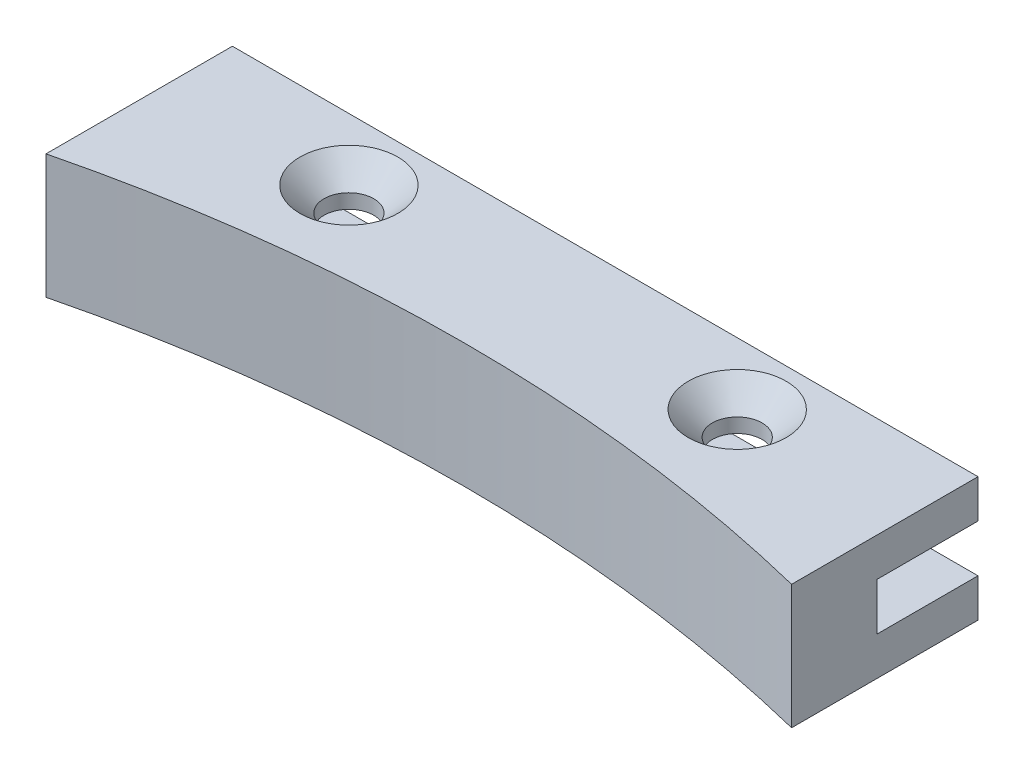
SolidWorks part; units mm, degrees
material "6061-T6 (SS)"
ref_plane "Front Plane" through (0, 0, 0) normal (0, 0, 1) x (1, 0, 0)
ref_plane "Top Plane" through (0, 0, 0) normal (0, 1, 0) x (1, 0, 0)
ref_plane "Right Plane" through (0, 0, 0) normal (1, 0, 0) x (0, 0, -1)
sketch "Sketch1" plane through (0, 0, 0) normal (0, 1, 0) x (1, 0, 0)
  line L0 (-24, 0) -> (24, 0)
  line L1 (24, 0) -> (24, -12)
  line L2 (-24, 0) -> (-24, -12)
  line L3 (-24, -9.0773) -> (24, -9.0773) construction
  line L25 (-24, -12) -> (0, -109.0773) construction
  line L26 (0, -109.0773) -> (24, -12) construction
  arc A0 (-24, -12) -> (24, -12) centre (0, -109.0773) cw
  point P0 (0, 0)
  dimension "D1" = 12
  dimension "D2" = 100
  dimension "D5" = 48
extrude "Boss-Extrude1" add sketch "Sketch1" along normal mid plane 8
hole_wizard "CSK for M3 Flat Head Machine Screw1" positions "Sketch10" profile "Sketch11" countersink size "M3" standard "ANSI Metric" end condition through all
sketch "Sketch10" plane through (0, 4, 0) normal (0, 1, 0) x (1, 0, 0)
  line L0 (0, -0.121) -> (0, -16.3024) construction
  line L1 (24, 0) -> (-24, 0) construction
  point P8 (-12.5, -4)
  point P13 (12.5, -4)
  dimension "D1" = 12.5
  dimension "D2" = 4
sketch "Sketch11" plane through (12.5, 4, 4) normal (1, 0, 0) x (0, 0, 1)
  line L0 (0, 0) -> (0, 8)
  line L1 (0, 8) -> (1.6, 8)
  line L2 (1.6, 8) -> (1.6, 1.55)
  line L3 (1.6, 1.55) -> (3.15, 0)
  line L5 (3.15, 0) -> (0, 0)
  line L6 (-1.6, 1.55) -> (-3.15, 0) construction
  line L11 (0, -6.35) -> (0, 107.95) construction
  dimension "Thru Hole Dia." = 3.2
  dimension "Thru Hole Depth" = 8
  dimension "Near C'Sink Dia." = 6.3
  dimension "Near C'Sink Angle" = 90
sketch "Sketch9" plane through (-24, 0, 0) normal (-1, 0, 0) x (0, 0, 1)
  line L0 (0, 4) -> (0, -4) construction
  line L1 (0, -1.525) -> (6.5, -1.525)
  line L2 (0, -1.525) -> (0, 1.525)
  line L3 (0, 1.525) -> (6.5, 1.525)
  line L4 (6.5, -1.525) -> (6.5, 1.525)
  point P6 (0, 0)
  dimension "D1" = 3.05
  dimension "D2" = 6.5
extrude "Cut-Extrude2" cut sketch "Sketch9" against normal through all
